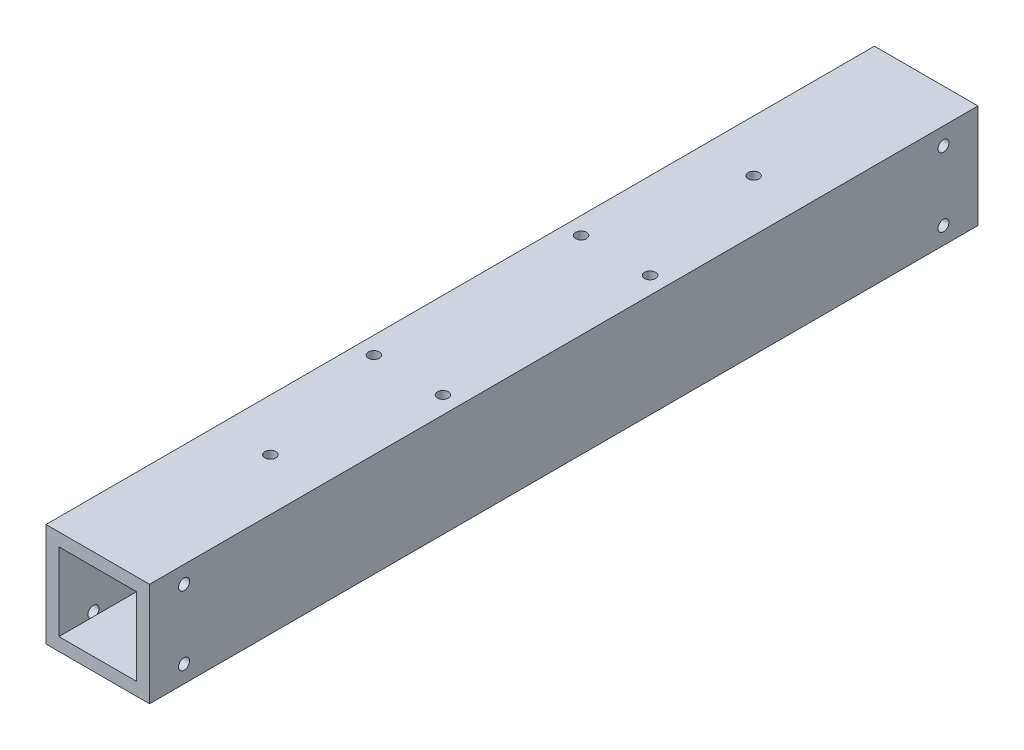
SolidWorks part; units mm, degrees
material "6061 Alloy"
ref_plane "Front Plane" through (0, 0, 0) normal (0, 0, 1) x (1, 0, 0)
ref_plane "Top Plane" through (0, 0, 0) normal (0, 1, 0) x (1, 0, 0)
ref_plane "Right Plane" through (0, 0, 0) normal (1, 0, 0) x (0, 0, -1)
sketch "Sketch1" plane through (0, 0, 0) normal (0, 1, 0) x (1, 0, 0)
  line L1 (-19.05, 152.4) -> (19.05, 152.4)
  line L2 (-19.05, 152.4) -> (-19.05, -152.4)
  line L3 (-19.05, -152.4) -> (19.05, -152.4)
  line L4 (19.05, 152.4) -> (19.05, -152.4)
  dimension "D1" = 19.05
  dimension "D2" = 19.05
  dimension "D3" = 152.4
  dimension "D4" = 152.4
extrude "Boss-Extrude1" add sketch "Sketch1" along normal mid plane 38.1
sketch "Sketch2" plane through (0, 0, 152.4) normal (0, 0, 1) x (1, 0, 0)
  line L0 (-19.05, 19.05) -> (-19.05, -19.05) construction
  line L1 (-14.2875, 14.2875) -> (14.2875, 14.2875)
  line L2 (-14.2875, 14.2875) -> (-14.2875, -14.2875)
  line L3 (-14.2875, -14.2875) -> (14.2875, -14.2875)
  line L4 (14.2875, 14.2875) -> (14.2875, -14.2875)
  line L5 (19.05, 19.05) -> (19.05, -19.05) construction
  line L6 (-19.05, -19.05) -> (19.05, -19.05) construction
  line L7 (-19.05, 19.05) -> (19.05, 19.05) construction
  dimension "D1" = 4.7625
  dimension "D2" = 4.7625
  dimension "D3" = 4.7625
  dimension "D4" = 4.7625
extrude "Cut-Extrude1" cut sketch "Sketch2" against normal through all
hole_wizard "#10-32 Tapped Hole1" positions "Sketch4" profile "Sketch3" tap size "#10-32" standard "ANSI Inch" end condition up to next
sketch "Sketch4" plane through (19.05, 0, 0) normal (1, 0, 0) x (0, 0, -1)
  line L0 (-152.4, 19.05) -> (-152.4, -19.05) construction
  point P0 (-139.7, 12.7)
  point P2 (-139.7, -12.7)
  dimension "D1" = 12.7
  dimension "D2" = 12.7
  dimension "D3" = 12.7
sketch "Sketch3" plane through (19.05, 12.7, 139.7) normal (0, 1, 0) x (0, 0, -1)
  line L0 (0, 0) -> (0, 4.7635)
  line L1 (0, 4.7635) -> (2.0193, 4.7635)
  line L2 (2.0193, 4.7635) -> (2.0193, 0)
  line L5 (2.0193, 0) -> (0, 0)
  line L11 (0, -6.35) -> (0, 107.95) construction
  dimension "Thru Tap Drill Dia." = 4.0386
  dimension "Thru Tap Drill Depth" = 4.7635
cosmetic thread "Hole Thread1" parameters "D2"=4.826
cosmetic thread "Hole Thread2" parameters "D2"=4.826
hole_wizard "#10-32 Tapped Hole2" positions "Sketch6" profile "Sketch5" tap size "#10-32" standard "ANSI Inch" end condition up to next
sketch "Sketch6" plane through (0, 19.05, 0) normal (0, 1, 0) x (1, 0, 0)
  point P0 (-12.7, -38.1)
  point P2 (12.7, -38.1)
  dimension "D1" = 12.7
  dimension "D2" = 12.7
  dimension "D3" = 38.1
sketch "Sketch5" plane through (-12.7, 19.05, 38.1) normal (1, 0, 0) x (0, 0, 1)
  line L0 (0, 0) -> (0, 4.7635)
  line L1 (0, 4.7635) -> (2.0193, 4.7635)
  line L2 (2.0193, 4.7635) -> (2.0193, 0)
  line L5 (2.0193, 0) -> (0, 0)
  line L11 (0, -6.35) -> (0, 107.95) construction
  dimension "Thru Tap Drill Dia." = 4.0386
  dimension "Thru Tap Drill Depth" = 4.7635
cosmetic thread "Hole Thread3" parameters "D2"=4.826
cosmetic thread "Hole Thread4" parameters "D2"=4.826
mirror "Mirror1" about plane through (0, 0, 0) normal (1, 0, 0) of "#10-32 Tapped Hole1"
mirror "Mirror3" about plane through (0, 0, 0) normal (0, 1, 0) of "#10-32 Tapped Hole2"
mirror "Mirror4" about plane through (0, 0, 0) normal (0, 0, 1) of "Mirror3", "Mirror1", "#10-32 Tapped Hole2", "#10-32 Tapped Hole1"
hole_wizard "#10-32 Tapped Hole3" positions "Sketch10" profile "Sketch9" tap size "#10-32" standard "ANSI Inch" end condition up to next
sketch "Sketch10" plane through (0, 19.05, 0) normal (0, 1, 0) x (1, 0, 0)
  point P0 (0, -88.9)
  point P4 (0, 88.9)
  dimension "D1" = 88.9
  dimension "D2" = 88.9
sketch "Sketch9" plane through (0, 19.05, 88.9) normal (1, 0, 0) x (0, 0, 1)
  line L0 (0, 0) -> (0, 38.1)
  line L1 (0, 38.1) -> (2.0193, 38.1)
  line L2 (2.0193, 38.1) -> (2.0193, 0)
  line L5 (2.0193, 0) -> (0, 0)
  line L11 (0, -6.35) -> (0, 107.95) construction
  dimension "Thru Tap Drill Dia." = 4.0386
  dimension "Thru Tap Drill Depth" = 38.1
cosmetic thread "Hole Thread5" parameters "D2"=4.826
cosmetic thread "Hole Thread6" parameters "D2"=4.826
mirror "Mirror5" about plane through (0, 0, 0) normal (0, 1, 0) of "#10-32 Tapped Hole3"
hole_wizard "15/64 (0.23438) Diameter Hole1" positions "Sketch12" profile "Sketch11" hole size "15/64" standard "ANSI Inch"
sketch "Sketch12" plane through (0, -19.05, 0) normal (0, -1, 0) x (-1, 0, 0)
  point P0 (0, -63.5)
  point P6 (-15.875, 63.5)
  point P8 (15.875, 63.5)
  dimension "D1" = 63.5
  dimension "D2" = 63.5
  dimension "D3" = 15.875
  dimension "D4" = 15.875
sketch "Sketch11" plane through (0, -19.05, 63.5) normal (1, 0, 0) x (0, 0, -1)
  line L0 (0, 0) -> (0, 3.0585)
  line L1 (0, 3.0585) -> (2.9766, 1.27)
  line L2 (2.9766, 1.27) -> (2.9766, 0)
  line L5 (2.9766, 0) -> (0, 0)
  line L10 (0, 3.0585) -> (-2.9766, 1.27) construction
  line L11 (0, -6.35) -> (0, 107.95) construction
  dimension "Hole Dia." = 5.9533
  dimension "Hole Depth" = 1.27
  dimension "Drill Angle" = 118
sketch "Sketch13" plane through (0, -19.05, 0) normal (0, -1, 0) x (1, 0, 0)
  line L0 (10.4175, -4.1814) -> (8.83, -6.9311)
  line L1 (-1.5875, 7.9375) -> (1.5875, 7.9375)
  line L2 (-1.5875, 7.9375) -> (-1.5875, 11.1125)
  line L3 (-1.5875, 11.1125) -> (1.5875, 11.1125)
  line L4 (1.5875, 7.9375) -> (1.5875, 11.1125)
  line L5 (-1.5875, 7.9375) -> (1.5875, 11.1125) construction
  line L6 (-1.5875, 11.1125) -> (1.5875, 7.9375) construction
  line L7 (7.6678, -2.5939) -> (10.4175, -4.1814)
  line L8 (6.0803, -5.3436) -> (8.83, -6.9311)
  line L9 (7.6678, -2.5939) -> (6.0803, -5.3436)
  line L10 (-8.83, -6.9311) -> (-10.4175, -4.1814)
  line L11 (-6.0803, -5.3436) -> (-8.83, -6.9311)
  line L12 (-7.6678, -2.5939) -> (-10.4175, -4.1814)
  line L13 (-6.0803, -5.3436) -> (-7.6678, -2.5939)
  circle A0 centre (0, 0) radius 9.525
  circle A1 centre (0, 0) radius 9.525
  circle A2 centre (0, 0) radius 9.525
  point P3 (0, 9.525)
  point P21 (0, 0)
  dimension "D1" = 3.175
  dimension "D2" = 3.175
  dimension "D3" = 3
extrude "Cut-Extrude2" cut sketch "Sketch13" against normal blind 1.5875 contours L4 A0 L2 L1 | A0 L4 L3 L2 | L12 A0 L11 L13 | A0 L12 L10 L11 | L8 A0 L7 L9 | A0 L8 L0 L7 region at (8.9167, -19.05, -5.1481) region at (7.5428, -19.05, -4.3548) region at (-7.5428, -19.05, -4.3548) region at (-8.9167, -19.05, -5.1481) region at (0, -19.05, 10.2961) region at (0, -19.05, 8.7096)
hole_wizard "#6-32 Tapped Hole1" positions "Sketch15" profile "Sketch16" tap size "#6-32" standard "ANSI Inch" end condition up to next
sketch "Sketch15" plane through (0, -19.05, 0) normal (0, -1, 0) x (-1, 0, 0)
  point P0 (0, 7.9375)
  point P9 (6.8741, -3.9687)
  point P10 (-6.8741, -3.9688)
  point P12 (0, 0)
  dimension "D1" = 7.9375
  dimension "D2" = 3
sketch "Sketch16" plane through (0, -19.05, -7.9375) normal (1, 0, 0) x (0, 0, -1)
  line L0 (0, 0) -> (0, 4.7625)
  line L1 (0, 4.7625) -> (1.3525, 4.7625)
  line L2 (1.3525, 4.7625) -> (1.3525, 0)
  line L5 (1.3525, 0) -> (0, 0)
  line L11 (0, -6.35) -> (0, 107.95) construction
  dimension "Thru Tap Drill Dia." = 2.7051
  dimension "Thru Tap Drill Depth" = 4.7625
cosmetic thread "Hole Thread7" parameters "D2"=3.5052
cosmetic thread "Hole Thread8" parameters "D2"=3.5052
cosmetic thread "Hole Thread9" parameters "D2"=3.5052
